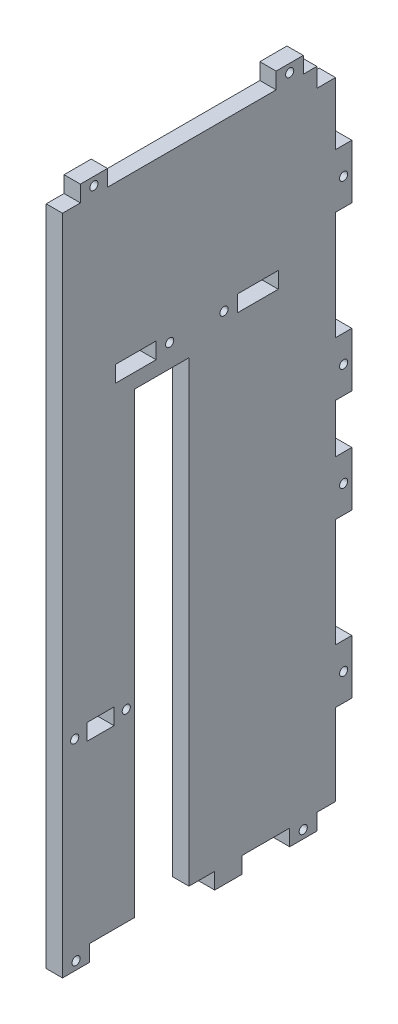
SolidWorks part; units mm, degrees
ref_plane "Plan de face" through (0, 0, 0) normal (0, 0, 1) x (1, 0, 0)
ref_plane "Plan de dessus" through (0, 0, 0) normal (0, 1, 0) x (1, 0, 0)
ref_plane "Plan de droite" through (0, 0, 0) normal (1, 0, 0) x (0, 0, -1)
sketch "Esquisse1" plane through (0, 0, 0) normal (1, 0, 0) x (0, 0, -1)
  line L0 (97.1531, 0) -> (-102.2664, 0) construction
  line L1 (-50.29, 119) -> (50.29, 119)
  line L2 (-50.29, 119) -> (-50.29, -119)
  line L3 (-50.29, -119) -> (50.29, -119)
  line L4 (50.29, 119) -> (50.29, -119)
  line L5 (0, 172.7153) -> (0, -236.1933) construction
  line L7 (-41.29, -48) -> (-31.29, -48)
  line L8 (-41.29, -48) -> (-41.29, -54)
  line L9 (-41.29, -54) -> (-31.29, -54)
  line L10 (-31.29, -48) -> (-31.29, -54)
  line L15 (-30.795, 61) -> (-15.795, 61)
  line L16 (-30.795, 61) -> (-30.795, 55)
  line L17 (-30.795, 55) -> (-15.795, 55)
  line L18 (-15.795, 61) -> (-15.795, 55)
  line L19 (14.205, 61) -> (29.205, 61)
  line L20 (14.205, 61) -> (14.205, 55)
  line L21 (14.205, 55) -> (29.205, 55)
  line L22 (29.205, 61) -> (29.205, 55)
  dimension "D1" = 238
  dimension "D2" = 100.58
  dimension "D4" = 119
  dimension "D13" = 15
  dimension "D14" = 15
  dimension "D15" = 30
  dimension "D16" = 6
  dimension "D17" = 6
  dimension "D3" = 50.29
  dimension "D5" = 58
  dimension "D6" = 19.495
  dimension "D7" = 9
  dimension "D8" = 167
  dimension "D9" = 6
  dimension "D10" = 10
extrude "Boss.-Extru.1" add sketch "Esquisse1" along normal blind 6
sketch "Esquisse3" plane through (6, 0, 0) normal (1, 0, 0) x (0, 0, -1)
  line L0 (-50.29, -119) -> (50.29, -119) construction
  line L1 (-50.29, -119) -> (-40.29, -119)
  line L2 (-50.29, -119) -> (-50.29, -125)
  line L3 (-50.29, -125) -> (-40.29, -125)
  line L4 (-40.29, -119) -> (-40.29, -125)
  line L5 (245.3741, 0) -> (-166.5298, 0) construction
  line L6 (50.29, -119) -> (50.29, 119) construction
  line L7 (33.41, -119) -> (43.41, -119)
  line L8 (33.41, -119) -> (33.41, -125)
  line L9 (33.41, -125) -> (43.41, -125)
  line L10 (0, 208.6671) -> (0, -232.3841) construction
  line L11 (-50.29, -119) -> (50.29, -119) construction
  line L12 (43.41, -119) -> (43.41, -125)
  line L13 (56.29, 29) -> (56.29, 9)
  line L14 (50.29, 9) -> (56.29, 9)
  line L15 (50.29, 29) -> (50.29, 9)
  line L16 (50.29, 29) -> (56.29, 29)
  line L17 (56.29, 89) -> (56.29, 69)
  line L18 (50.29, 69) -> (56.29, 69)
  line L19 (50.29, 89) -> (50.29, 69)
  line L20 (50.29, 89) -> (56.29, 89)
  line L21 (50.29, 119) -> (-50.29, 119) construction
  line L22 (50.29, -89) -> (56.29, -89)
  line L23 (50.29, -89) -> (50.29, -69)
  line L24 (50.29, -69) -> (56.29, -69)
  line L25 (56.29, -89) -> (56.29, -69)
  line L26 (50.29, -29) -> (56.29, -29)
  line L27 (50.29, -29) -> (50.29, -9)
  line L28 (50.29, -9) -> (56.29, -9)
  line L29 (0, -208.6671) -> (0, 232.3841) construction
  line L30 (5.79, -119) -> (15.79, -119)
  line L31 (5.79, -119) -> (5.79, -125)
  line L32 (5.79, -125) -> (15.79, -125)
  line L33 (15.79, -119) -> (15.79, -125)
  line L34 (50.29, -119) -> (50.29, 119) construction
  line L35 (56.29, -29) -> (56.29, -9)
  line L36 (38.41, 119) -> (28.41, 119)
  line L37 (38.41, 119) -> (38.41, 125)
  line L38 (38.41, 125) -> (28.41, 125)
  line L39 (28.41, 119) -> (28.41, 125)
  line L40 (-50.29, 119) -> (-50.29, -119) construction
  line L41 (-33.71, 119) -> (-43.71, 119)
  line L42 (-33.71, 119) -> (-33.71, 125)
  line L43 (-33.71, 125) -> (-43.71, 125)
  line L44 (-43.71, 119) -> (-43.71, 125)
  dimension "D2" = 10
  dimension "D3" = 6
  dimension "D4" = 10
  dimension "D5" = 6.88
  dimension "D6" = 6
  dimension "D7" = 6
  dimension "D8" = 20
  dimension "D9" = 6
  dimension "D10" = 20
  dimension "D11" = 6
  dimension "D12" = 10
  dimension "D13" = 17.62
  dimension "D14" = 30
  dimension "D15" = 40
  dimension "D16" = 6
  dimension "D17" = 10
  dimension "D18" = 11.88
  dimension "D19" = 6.58
  dimension "D20" = 10
  dimension "D21" = 6
extrude "Boss.-Extru.5" add sketch "Esquisse3" against normal blind 6
sketch "Esquisse6" plane through (6, 0, 0) normal (1, 0, 0) x (0, 0, -1)
  line L0 (-40.29, -119) -> (5.79, -119) construction
  line L1 (-23.71, -119) -> (-3.71, -119)
  line L2 (-23.71, -119) -> (-23.71, 49.59)
  line L3 (-23.71, 49.59) -> (-3.71, 49.59)
  line L4 (-3.71, -119) -> (-3.71, 49.59)
  line L5 (50.29, -69) -> (50.29, -29) construction
  line L8 (28.41, 119) -> (-33.71, 119) construction
  dimension "D1" = 20
  dimension "D2" = 69.41
  dimension "D3" = 54
extrude "Enlèv. mat.-Extru.2" cut sketch "Esquisse6" against normal blind 6
sketch "Esquisse7" plane through (0, 0, 0) normal (-1, 0, 0) x (0, 0, 1)
  line L1 (-50.29, 119) -> (-43.41, 119)
  line L2 (-50.29, 119) -> (-50.29, 112)
  line L3 (-50.29, 112) -> (-43.41, 112)
  line L4 (-43.41, 119) -> (-43.41, 112)
  dimension "D1" = 7
  dimension "D2" = 6.88
extrude "Enlèv. mat.-Extru.3" cut sketch "Esquisse7" against normal blind 6
sketch "Esquisse8" plane through (0, 0, 0) normal (-1, 0, 0) x (0, 0, 1)
  line L0 (-51.0214, 58) -> (44.3386, 58) construction
  line L1 (50.29, -125) -> (40.29, -125) construction
  line L2 (-14.205, 61) -> (-14.205, 55) construction
  line L3 (15.795, 55) -> (15.795, 61) construction
  line L5 (60.5401, -51) -> (10.4957, -51) construction
  line L6 (41.29, -48) -> (41.29, -54) construction
  line L7 (31.29, -54) -> (31.29, -48) construction
  line L8 (41.29, -54) -> (31.29, -54) construction
  line L9 (53.2872, 122) -> (-67.0711, 122) construction
  line L10 (33.71, 125) -> (43.71, 125) construction
  line L11 (-28.41, 125) -> (-28.41, 119) construction
  line L12 (33.71, 119) -> (33.71, 125) construction
  line L13 (-67.0711, -122) -> (72.8873, -122) construction
  line L16 (-33.41, -119) -> (-33.41, -125) construction
  line L17 (40.29, -125) -> (40.29, -119) construction
  line L18 (-53.29, 135.0788) -> (-53.29, -173.0788) construction
  line L19 (-56.29, 69) -> (-56.29, 89) construction
  line L21 (-56.29, -69) -> (-50.29, -69) construction
  line L22 (-50.29, 9) -> (-56.29, 9) construction
  line L23 (-56.29, 89) -> (-50.29, 89) construction
  circle A1 centre (-9.205, 58) radius 1.5
  circle A2 centre (10.795, 58) radius 1.5
  circle A4 centre (26.79, -51) radius 1.5
  circle A5 centre (45.79, -51) radius 1.5
  circle A6 centre (38.71, 122) radius 1.5
  circle A7 centre (-33.41, 122) radius 1.5
  circle A8 centre (45.29, -122) radius 1.5
  circle A9 centre (-53.29, 79) radius 1.5
  circle A10 centre (-38.41, -122) radius 1.5
  circle A11 centre (-53.29, 19) radius 1.5
  circle A12 centre (-53.29, -79) radius 1.5
  circle A13 centre (-53.29, -19) radius 1.5
  dimension "D1" = 3
  dimension "D2" = 3
  dimension "D4" = 3
  dimension "D6" = 5
  dimension "D7" = 5
  dimension "D9" = 3
  dimension "D10" = 3
  dimension "D15" = 3
  dimension "D16" = 3
  dimension "D17" = 5
  dimension "D18" = 5
  dimension "D20" = 3
  dimension "D21" = 3
  dimension "D22" = 3
  dimension "D23" = 3
  dimension "D24" = 5
  dimension "D25" = 5
  dimension "D26" = 3
  dimension "D27" = 3
  dimension "D28" = 3
  dimension "D29" = 10
  dimension "D31" = 10
  dimension "D32" = 10
  dimension "D11" = 4.5
  dimension "D12" = 4.5
  dimension "D13" = 3
  dimension "D14" = 3
  dimension "D30" = 10
extrude "Enlèv. mat.-Extru.4" cut sketch "Esquisse8" against normal blind 6
equation "\"D3@Esquisse1\"=\"D2@Esquisse1\"/2"
equation "\"D4@Esquisse1\"=\"D1@Esquisse1\"/2"
